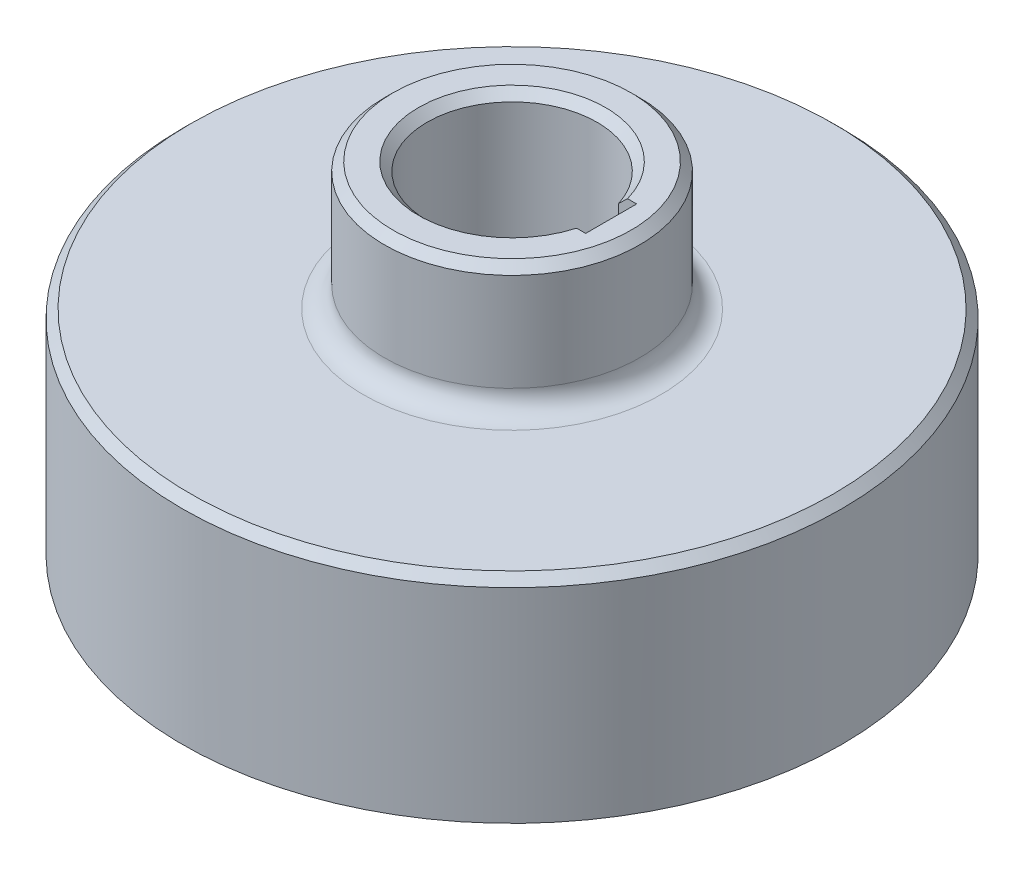
SolidWorks part; units mm, degrees
other "Markup1"
sketch "Sketch7" plane through (-77.5, 0, -77.5) normal (-0.5198, -0.8294, -0.2047) x (0.8494, -0.5274, -0.0202)
material "0.7060 (EN-GJS-600-3)"
ref_plane "Front Plane" through (0, 0, 0) normal (0, 0, 1) x (1, 0, 0)
ref_plane "Top Plane" through (0, 0, 0) normal (0, 1, 0) x (1, 0, 0)
ref_plane "Right Plane" through (0, 0, 0) normal (1, 0, 0) x (0, 0, -1)
sketch "Sketch1" plane through (0, 0, 0) normal (0, 0, 1) x (1, 0, 0)
  line L0 (0, -1292.3904) -> (0, 63327.1275) construction
  line L1 (20, 80) -> (30, 80)
  line L2 (30, 80) -> (30, 50)
  line L3 (30, 50) -> (77.5, 50)
  line L4 (77.5, 50) -> (77.5, 0)
  line L5 (77.5, 0) -> (63, 0)
  line L7 (70, 40) -> (25, 40)
  line L8 (20, 45) -> (20, 80)
  line L9 (70, 40) -> (70, 35)
  line L10 (63, 0) -> (63, 35)
  line L11 (63, 35) -> (70, 35)
  line L12 (25, 40) -> (25, 45)
  line L13 (25, 45) -> (20, 45)
  dimension "D1" = 40
  dimension "D2" = 5
  dimension "D3" = 5
  dimension "D4" = 155
  dimension "D5" = 10
  dimension "D6" = 60
  dimension "D7" = 126
  dimension "D8" = 140
  dimension "D9" = 35
  dimension "D10" = 40
  dimension "D11" = 5
revolve "Revolve1" add sketch "Sketch1" angle 360 about L0
fillet "Fillet1" radius 1.5 1 edges at (70, 40, 0)
sketch "Sketch2" plane through (0, 0, 0) normal (0, -1, 0) x (1, 0, 0)
  line L0 (0, -1000) -> (0, 49000) construction
  line L1 (-6.125, 68.8) -> (6.125, 68.8)
  line L2 (6.125, 68.8) -> (6.125, 62.7016)
  line L3 (-6.125, 68.8) -> (-6.125, 62.7016)
  circle A0 centre (0, 0) radius 63 construction
  arc A1 (6.125, 62.7016) -> (-6.125, 62.7016) centre (0, 0) ccw
  point P5 (0, 68.8)
  dimension "D1" = 12.25
  dimension "D2" = 68.8
extrude "Cut-Extrude1" cut sketch "Sketch2" against normal up to surface (35 mm away) up to face at (63, 35, 0)
fillet "Fillet2" radius 2 2 edges at (6.125, 17.5, 62.7016) (-6.125, 17.5, 62.7016)
pattern_circular "CirPattern1" count 6 over 360 about axis through (0, -1292.3904, 0) along (0, -1, 0) of "Cut-Extrude1", "Fillet2" reverse direction yes
fillet "Fillet3" radius 5 1 edges at (30, 50, 0)
chamfer "Chamfer1" distance 2 angle 45 3 edges at (30, 80, 0) (77.5, 50, 0) (20, 80, 0)
chamfer "Chamfer3" distance 1 angle 45 2 edges at (25, 40, 0) (20, 45, 0)
ref_plane "Plane1" through (23.3, 0, 0) normal (1, 0, 0) x (0, 0, -1)
sketch "Sketch3" plane through (23.3, 0, 0) normal (1, 0, 0) x (0, 0, -1)
  line L0 (28, 80) -> (-28, 80) construction
  line L1 (-6, 80) -> (6, 80)
  line L2 (-6, 80) -> (-6, 45)
  line L3 (-6, 45) -> (6, 45)
  line L4 (6, 80) -> (6, 45)
  line L6 (-21, 45) -> (21, 45) construction
  point P6 (0, 80)
  dimension "D1" = 12
extrude "Cut-Extrude2" cut sketch "Sketch3" against normal up to next
sketch "Sketch6" plane through (0, 0, 0) normal (0, 0, 1) x (1, 0, 0)
  line L0 (-70.25, -967.9081) -> (-70.25, 49032.0919) construction
  line L3 (-77.5, 0) -> (-63, 0) construction
  line L5 (-68.183, 0) -> (-68.183, 10)
  line L6 (-68.183, 10) -> (-70.25, 11.1934)
  line L7 (-70.25, 11.1934) -> (-70.25, 0)
  line L8 (-70.25, 0) -> (-68.183, 0)
  point P1 (-63, 0)
  point P11 (-70.25, 0)
  dimension "D1" = 60
  dimension "D2" = 4.134
  dimension "D3" = 10
revolve "Cut-Revolve1" cut sketch "Sketch6" angle 360 about L0
chamfer "Chamfer4" distance 0.5 angle 45 1 edges at (-70.25, 0, -2.067)
pattern_circular "CirPattern2" count 6 over 360 about axis through (0, -1292.3904, 0) along (0, -1, 0) of "Cut-Revolve1", "Chamfer4"
